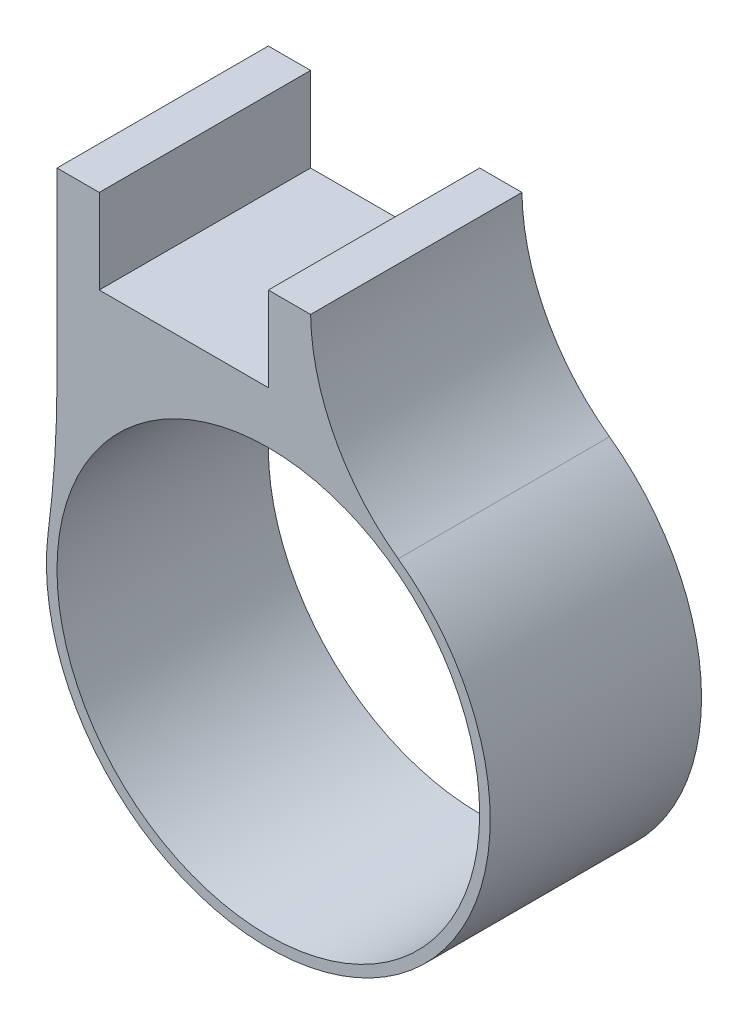
SolidWorks part; units mm, degrees
material "Thornel VCB-20 Carbon Cloth"
ref_plane "Спереди" through (0, 0, 0) normal (0, 0, 1) x (1, 0, 0)
ref_plane "Сверху" through (0, 0, 0) normal (0, 1, 0) x (1, 0, 0)
ref_plane "Справа" through (0, 0, 0) normal (1, 0, 0) x (0, 0, -1)
other "Configuration Table"
sketch "Sketch1" plane through (0, 0, 0) normal (0, 0, 1) x (1, 0, 0)
  line L0 (-10, 16.4554) -> (-10, 3.2016)
  line L1 (0, 16.4554) -> (2, 16.4554)
  line L2 (0, 16.4554) -> (0, 12.4554)
  line L4 (2, 16.4554) -> (2, 10.3078)
  line L5 (-10, 16.4554) -> (-8, 16.4554)
  line L8 (-8, 16.4554) -> (-8, 12.4554)
  line L9 (0, 12.4554) -> (-8, 12.4554)
  circle A0 centre (0, 0) radius 10
  circle A1 centre (0, 0) radius 10.5
  point P17 (-4, 12.4554)
  dimension "D1" = 20
  dimension "D2" = 21
  dimension "D3" = 4
  dimension "D4" = 2
  dimension "D5" = 8
  dimension "D6" = 2
extrude "Boss-Extrude1" add sketch "Sketch1" along normal blind 10 contours A1 L4 L1 L2 L9 L8 L5 L0 | A1 A0 region at (-5.2092, 11.318, 0) region at (-5.1989, 8.7791, 0)
fillet "Fillet1" radius 50 1 edges at (-10, 3.2016, 5)
fillet "Fillet2" radius 10 1 edges at (2, 10.3078, 5)
